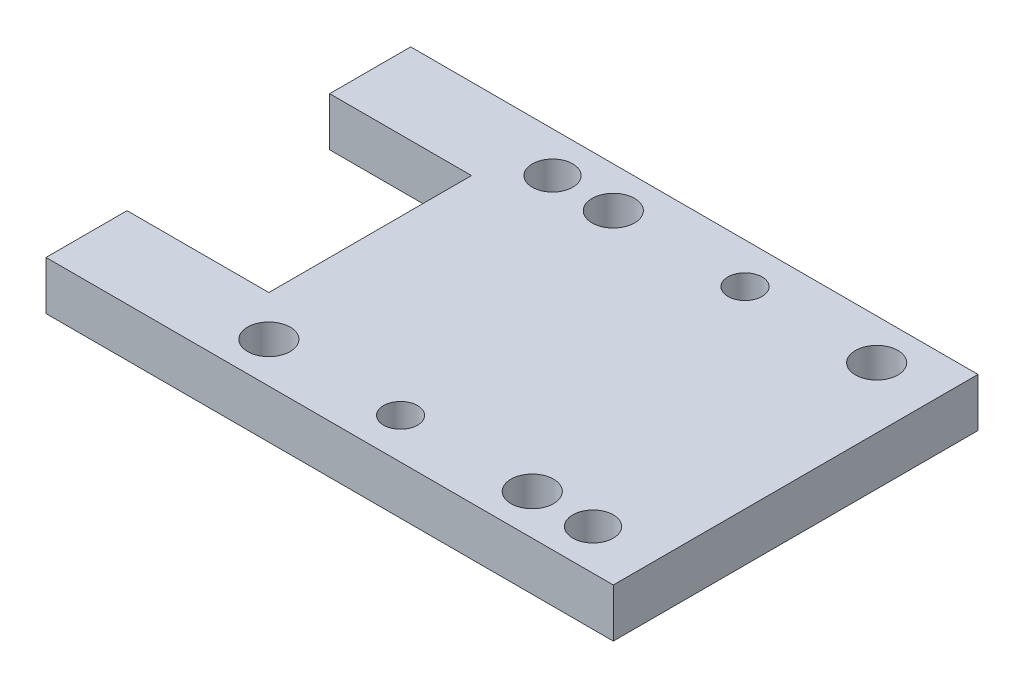
SolidWorks part; units mm, degrees
material "K110"
ref_plane "Front Plane" through (0, 0, 0) normal (0, 0, 1) x (1, 0, 0)
ref_plane "Top Plane" through (0, 0, 0) normal (0, 1, 0) x (1, 0, 0)
ref_plane "Right Plane" through (0, 0, 0) normal (1, 0, 0) x (0, 0, -1)
sketch "Sketch1" plane through (0, 0, 0) normal (0, 1, 0) x (1, 0, 0)
  line L1 (-70, -45) -> (70, -45)
  line L2 (-70, -45) -> (-70, 45)
  line L3 (-70, 45) -> (70, 45)
  line L4 (70, -45) -> (70, 45)
  line L5 (-70, -45) -> (70, 45) construction
  line L6 (-70, 45) -> (70, -45) construction
  point P0 (0, 0)
  dimension "D1" = 90
  dimension "D2" = 140
extrude "Boss-Extrude1" add sketch "Sketch1" against normal blind 12
sketch "Sketch2" plane through (0, 0, 0) normal (0, 1, 0) x (1, 0, 0)
  line L0 (-70, 45) -> (-70, -45) construction
  line L1 (-70, -25) -> (-35, -25)
  line L2 (-70, -25) -> (-70, 25)
  line L3 (-70, 25) -> (-35, 25)
  line L4 (-35, -25) -> (-35, 25)
  point P6 (-35, 0)
  dimension "D1" = 50
  dimension "D2" = 35
extrude "Cut-Extrude1" cut sketch "Sketch2" against normal up to next
hole_wizard "M10 Clearance Hole1" positions "Sketch6" profile "Sketch4" hole size "M10" standard "ISO" end condition through all
sketch "Sketch6" plane through (0, 0, 0) normal (0, 1, 0) x (1, 0, 0)
  point P12 (-10, 35)
  point P15 (55, 35)
  point P18 (40, -35)
  point P21 (-25, -35)
sketch "Sketch4" plane through (-10, 0, -35) normal (1, 0, 0) x (0, 0, 1)
  line L0 (0, 0) -> (0, 12)
  line L1 (0, 12) -> (5.25, 12)
  line L2 (5.25, 12) -> (5.25, 0)
  line L5 (5.25, 0) -> (0, 0)
  line L11 (0, -6.35) -> (0, 107.95) construction
  dimension "Thru Hole Dia." = 10.5
  dimension "Thru Hole Depth" = 12
hole_wizard "Ø10.0mm Dowel Hole1" positions "Sketch9" profile "Sketch8" hole size "Ø10.0" standard "ISO" end condition through all
sketch "Sketch9" plane through (0, 0, 0) normal (0, 1, 0) x (1, 0, 0)
  point P0 (-25, 35)
  point P3 (55, -35)
sketch "Sketch8" plane through (-25, 0, -35) normal (1, 0, 0) x (0, 0, 1)
  line L0 (0, 0) -> (0, 12)
  line L1 (0, 12) -> (5, 12)
  line L2 (5, 12) -> (5, 0)
  line L5 (5, 0) -> (0, 0)
  line L11 (0, -6.35) -> (0, 107.95) construction
  dimension "Thru Hole Dia." = 10
  dimension "Thru Hole Depth" = 12
hole_wizard "M8 Tapped Hole1" positions "Sketch12" profile "Sketch11" tap size "M8" standard "ISO"
sketch "Sketch12" plane through (-70, 0, 0) normal (-1, 0, 0) x (0, 0, 1)
  line L0 (45, -12) -> (45, 0) construction
  line L1 (-45, 0) -> (-25, 0) construction
  line L2 (25, 0) -> (45, 0) construction
  point P0 (35, -6)
  point P2 (-35, -6)
  point P7 (45, -6)
  point P10 (-35, 0)
  point P13 (35, 0)
sketch "Sketch11" plane through (-70, -6, 35) normal (0, 1, 0) x (0, 0, 1)
  line L0 (0, 0) -> (0, 22.25)
  line L1 (0, 22.25) -> (3.4, 20.2071)
  line L2 (3.4, 20.2071) -> (3.4, 0)
  line L5 (3.4, 0) -> (0, 0)
  line L10 (0, 22.25) -> (-3.4, 20.2071) construction
  line L11 (0, -6.35) -> (0, 107.95) construction
  dimension "Tap Drill Dia." = 6.8
  dimension "Tap Drill Depth" = 22.25
  dimension "Drill Angle" = 118
cosmetic thread "Hole Thread1"
cosmetic thread "Hole Thread2"
hole_wizard "M8 Clearance Hole1" positions "Sketch15" profile "Sketch14" hole size "M8" standard "ISO" end condition through all
sketch "Sketch15" plane through (0, 0, 0) normal (0, 1, 0) x (1, 0, 0)
  point P0 (22.5, 35)
  point P3 (7.5, -35)
sketch "Sketch14" plane through (22.5, 0, -35) normal (1, 0, 0) x (0, 0, 1)
  line L0 (0, 0) -> (0, 12)
  line L1 (0, 12) -> (4.2, 12)
  line L2 (4.2, 12) -> (4.2, 0)
  line L5 (4.2, 0) -> (0, 0)
  line L11 (0, -6.35) -> (0, 107.95) construction
  dimension "Thru Hole Dia." = 8.4
  dimension "Thru Hole Depth" = 12
